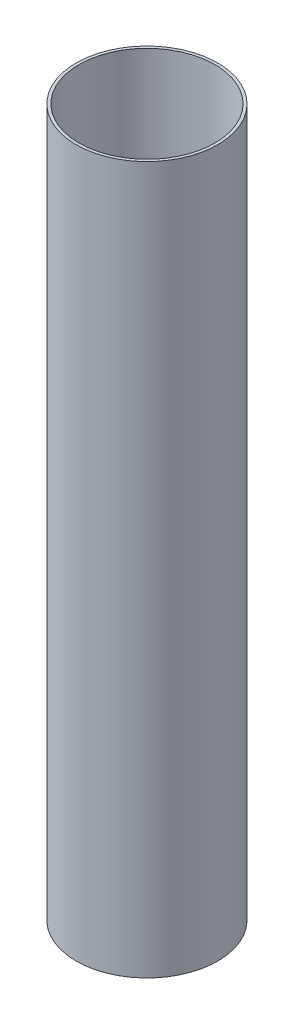
SolidWorks part; units mm, degrees
ref_plane "Front Plane" through (0, 0, 0) normal (0, 0, 1) x (1, 0, 0)
ref_plane "Top Plane" through (0, 0, 0) normal (0, 1, 0) x (1, 0, 0)
ref_plane "Right Plane" through (0, 0, 0) normal (1, 0, 0) x (0, 0, -1)
sketch "Sketch1" plane through (0, 0, 0) normal (0, 1, 0) x (1, 0, 0)
  circle A0 centre (0, 0) radius 39.6748
  circle A1 centre (0, 0) radius 38.1
  dimension "D1" = 79.3496
  dimension "D2" = 76.2
extrude "Boss-Extrude1" add sketch "Sketch1" along normal mid plane 396.24
equation "\"iDiameter\"= 3in"
equation "\"oDiameter\"= 3.124in"
equation "\"length\"= 15.6in"
equation "\"D1@Sketch1\"=\"oDiameter\""
equation "\"D2@Sketch1\"=\"iDiameter\""
equation "\"D1@Boss-Extrude1\"=\"length\""
